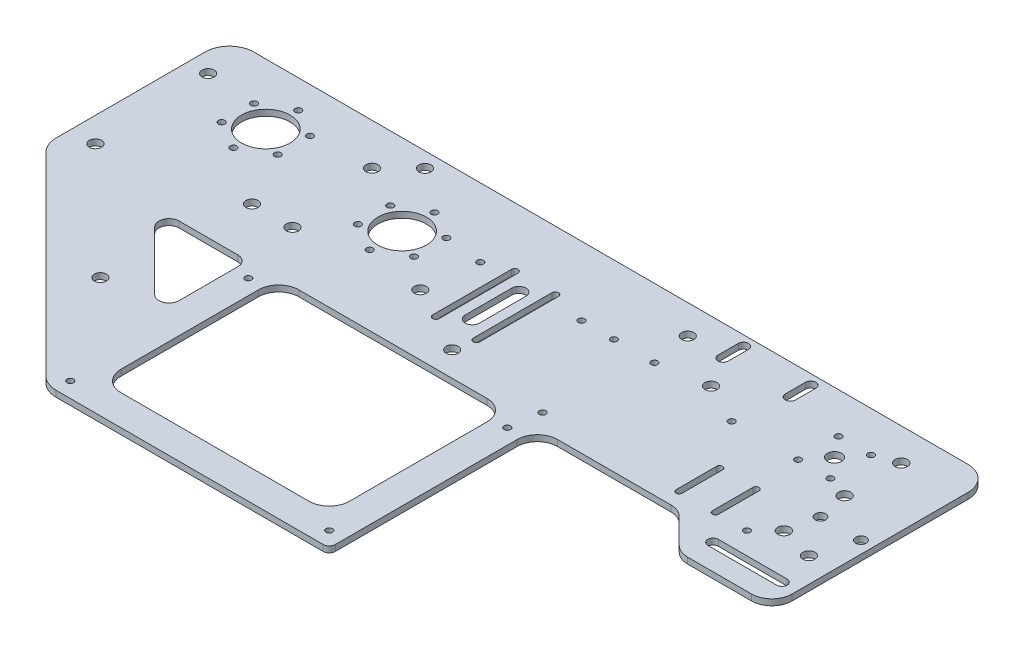
SolidWorks part; units mm, degrees
material "ACM"
ref_plane "Plano frontal" through (0, 0, 0) normal (0, 0, 1) x (1, 0, 0)
ref_plane "Plano superior" through (0, 0, 0) normal (0, 1, 0) x (1, 0, 0)
ref_plane "Plano direito" through (0, 0, 0) normal (1, 0, 0) x (0, 0, -1)
sketch "Esboço1" plane through (0, 0, 0) normal (0, 1, 0) x (1, 0, 0)
  line L3 (-80.5574, -153.6487) -> (51.4721, -153.6487)
  line L4 (54.4721, -150.6487) -> (54.4721, -60.7886)
  line L6 (188.5279, -40.7886) -> (188.5279, 28)
  line L7 (176.5279, 40) -> (-176.5279, 40)
  line L8 (-188.5279, 28) -> (-188.5279, -45.6781)
  line L12 (-122.5768, -50.7886) -> (-93.5279, -50.7886)
  line L13 (-88.5279, -55.7886) -> (-88.5279, -84.8375)
  line L14 (-97.0635, -88.373) -> (-126.1124, -59.3241)
  line L15 (39.4721, -60.6487) -> (39.4721, -128.6487)
  line L16 (29.4721, -138.6487) -> (-63.5279, -138.6487)
  line L17 (-73.5279, -128.6487) -> (-73.5279, -60.6487)
  line L18 (-63.5279, -50.6487) -> (29.4721, -50.6487)
  line L20 (132.5279, 0) -> (148.5279, 0) construction
  line L21 (132.5279, 0) -> (132.5279, 20) construction
  line L22 (132.5279, 20) -> (148.5279, 20) construction
  line L23 (148.5279, 0) -> (148.5279, 20) construction
  line L24 (132.5279, 0) -> (148.5279, 20) construction
  line L25 (132.5279, 20) -> (148.5279, 0) construction
  line L30 (64.4721, -50.7886) -> (178.5279, -50.7886)
  line L31 (134.7221, -43) -> (134.7221, -23) construction
  line L32 (133.2221, -43) -> (133.2221, -23)
  line L33 (136.2221, -43) -> (136.2221, -23)
  line L34 (125.7221, -45.2211) -> (125.7221, -21.4375) construction
  line L36 (116.7221, -43) -> (116.7221, -23) construction
  line L37 (118.2221, -43) -> (118.2221, -23)
  line L38 (115.2221, -43) -> (115.2221, -23)
  line L40 (54.4721, -120.5) -> (144.9721, -120.5) construction
  line L41 (54.4721, -120.5) -> (54.4721, -7) construction
  line L42 (54.4721, -7) -> (144.9721, -7) construction
  line L43 (144.9721, -120.5) -> (144.9721, -7) construction
  line L44 (54.4721, -120.5) -> (144.9721, -7) construction
  line L45 (54.4721, -7) -> (144.9721, -120.5) construction
  line L46 (70.5279, 25) -> (70.5279, 35) construction
  line L47 (67.9779, 25) -> (67.9779, 35)
  line L48 (73.0779, 25) -> (73.0779, 35)
  line L49 (103.7779, 25) -> (103.7779, 35) construction
  line L50 (101.2279, 25) -> (101.2279, 35)
  line L51 (106.3279, 25) -> (106.3279, 35)
  line L52 (-185.0132, -54.1634) -> (-89.0426, -150.134)
  circle A0 centre (-81.0279, -58.1487) radius 1.6
  circle A1 centre (-81.0279, -146.1487) radius 1.6
  circle A2 centre (46.9721, -58.1487) radius 1.6
  circle A3 centre (46.9721, -146.1487) radius 1.6
  circle A8 centre (176.311, -38.4318) radius 3
  circle A9 centre (0, -38.4318) radius 3
  circle A11 centre (-140.5279, 10) radius 12
  circle A20 centre (-140.5279, 10) radius 16 construction
  circle A21 centre (-140.5279, -6) radius 1.6
  circle A22 centre (-154.3843, 2) radius 1.6
  circle A23 centre (-154.3843, 18) radius 1.6
  circle A24 centre (-84.3674, 32.5) radius 3
  circle A25 centre (-176.311, -38.4318) radius 3
  circle A26 centre (140.5279, 10) radius 3.5
  circle A27 centre (148.5279, 0) radius 1.6
  circle A28 centre (148.5279, 20) radius 1.6
  circle A29 centre (132.5279, 0) radius 1.6
  circle A30 centre (132.5279, 20) radius 1.6
  arc A31 (51.4721, -153.6487) -> (54.4721, -150.6487) centre (51.4721, -150.6487) ccw
  arc A34 (188.5279, 28) -> (176.5279, 40) centre (176.5279, 28) ccw
  arc A35 (-176.5279, 40) -> (-188.5279, 28) centre (-176.5279, 28) ccw
  arc A39 (-93.5279, -50.7886) -> (-88.5279, -55.7886) centre (-93.5279, -55.7886) cw
  arc A40 (-88.5279, -84.8375) -> (-97.0635, -88.373) centre (-93.5279, -84.8375) cw
  arc A41 (-126.1124, -59.3241) -> (-122.5768, -50.7886) centre (-122.5768, -55.7886) cw
  arc A42 (39.4721, -128.6487) -> (29.4721, -138.6487) centre (29.4721, -128.6487) cw
  arc A43 (-63.5279, -138.6487) -> (-73.5279, -128.6487) centre (-63.5279, -128.6487) cw
  arc A44 (-73.5279, -60.6487) -> (-63.5279, -50.6487) centre (-63.5279, -60.6487) cw
  arc A45 (29.4721, -50.6487) -> (39.4721, -60.6487) centre (29.4721, -60.6487) cw
  circle A46 centre (-140.5279, 26) radius 1.6
  circle A47 centre (-126.6715, 18) radius 1.6
  circle A48 centre (-126.6715, 2) radius 1.6
  circle A49 centre (-63.1716, 0) radius 16 construction
  circle A50 centre (-63.1716, -16) radius 1.6
  circle A51 centre (-77.028, -8) radius 1.6
  circle A52 centre (-77.028, 8) radius 1.6
  circle A53 centre (-63.1716, 16) radius 1.6
  circle A54 centre (-49.3152, 8) radius 1.6
  circle A55 centre (-49.3152, -8) radius 1.6
  circle A56 centre (-63.1716, 0) radius 12
  circle A57 centre (-33.5279, -20.6487) radius 3
  circle A58 centre (79.5279, 10) radius 3
  arc A62 (188.5279, -40.7886) -> (178.5279, -50.7886) centre (178.5279, -40.7886) cw
  arc A63 (54.4721, -60.7886) -> (64.4721, -50.7886) centre (64.4721, -60.7886) cw
  arc A64 (133.2221, -43) -> (136.2221, -43) centre (134.7221, -43) ccw
  arc A65 (136.2221, -23) -> (133.2221, -23) centre (134.7221, -23) ccw
  arc A66 (118.2221, -43) -> (115.2221, -43) centre (116.7221, -43) cw
  arc A67 (115.2221, -23) -> (118.2221, -23) centre (116.7221, -23) cw
  circle A68 centre (99.7221, 0) radius 1.6
  circle A69 centre (49.2221, -43) radius 1.6
  circle A70 centre (134.7221, -43) radius 1.6 construction
  circle A71 centre (-30.5279, 6) radius 1.6
  circle A72 centre (19.4721, 6) radius 1.6
  circle A73 centre (55.5279, 6) radius 1.6
  circle A75 centre (35.5279, 6) radius 1.6
  circle A76 centre (70.5279, 30) radius 2.55 construction
  circle A77 centre (103.7779, 30) radius 2.55 construction
  circle A78 centre (159.4679, 24.07) radius 3.05
  circle A79 centre (159.4679, -3.93) radius 3.05
  circle A80 centre (159.4679, -33.93) radius 3.05
  arc A81 (67.9779, 25) -> (73.0779, 25) centre (70.5279, 25) ccw
  arc A82 (73.0779, 35) -> (67.9779, 35) centre (70.5279, 35) ccw
  arc A83 (101.2279, 25) -> (106.3279, 25) centre (103.7779, 25) ccw
  arc A84 (106.3279, 35) -> (101.2279, 35) centre (103.7779, 35) ccw
  circle A85 centre (-178.5279, 19.5) radius 3
  circle A86 centre (-97.5279, 19.5) radius 3
  arc A87 (-80.5574, -153.6487) -> (-89.0426, -150.134) centre (-80.5574, -141.6487) cw
  arc A88 (-185.0132, -54.1634) -> (-188.5279, -45.6781) centre (-176.5279, -45.6781) cw
  circle A89 centre (52.3279, 25.68) radius 3
  circle A90 centre (150.2221, -43) radius 1.6
  point P14 (134.7221, -33)
  point P43 (-140.5279, 10)
  point P70 (-144.4721, -50.6487)
  point P82 (-85.5279, -153.6487)
  point P116 (-63.1716, 0)
  point P123 (0, 40)
  point P124 (116.7221, -33)
  point P129 (99.7221, -63.75)
  point P141 (99.7221, -7)
  point P161 (70.5279, 30)
  point P168 (103.7779, 30)
  dimension "D2" = 3
  dimension "D8" = 12
  dimension "D10" = 12
  dimension "D11" = 61
  dimension "D12" = 203.9448
  dimension "D13" = 7.5
  dimension "D14" = 104.1605
  dimension "D16" = 135.7229
  dimension "D20" = 19.68
  dimension "D21" = 3.2
  dimension "D22" = 48.4318
  dimension "D23" = 32
  dimension "D24" = 3.2
  dimension "D25" = 6
  dimension "D26" = 24
  dimension "D27" = 48
  dimension "D28" = 30
  dimension "D29" = 40
  dimension "D30" = 6
  dimension "D34" = 30
  dimension "D31" = 32
  dimension "D32" = 3.2
  dimension "D33" = 24
  dimension "D35" = 6
  dimension "D36" = 155
  dimension "D37" = 30
  dimension "D44" = 7
  dimension "D48" = 10
  dimension "D54" = 50.5
  dimension "D6" = 10
  dimension "D58" = 5
  dimension "D62" = 1.5
  dimension "D72" = 85
  dimension "D75" = 5.1
  dimension "D80" = 14.07
  dimension "D82" = 6.1
  dimension "D83" = 10
  dimension "D19" = 6
  dimension "D47" = 101
  dimension "D1" = 137
  dimension "D9" = 377.0558
  dimension "D15" = 225
  dimension "D17" = 38
  dimension "D18" = 15
  dimension "D38" = 48
  dimension "D39" = 15
  dimension "D40" = 12.2169
  dimension "D41" = 12.2169
  dimension "D42" = 16
  dimension "D43" = 20
  dimension "D45" = 15
  dimension "D46" = 15
  dimension "D49" = 7.5
  dimension "D50" = 7.5
  dimension "D51" = 88
  dimension "D52" = 128
  dimension "D53" = 93
  dimension "D56" = 20.6487
  dimension "D57" = 68
  dimension "D59" = 10
  dimension "D60" = 20.5
  dimension "D61" = 20
  dimension "D63" = 9
  dimension "D64" = 113.5
  dimension "D65" = 90.5
  dimension "D66" = 7
  dimension "D67" = 43
  dimension "D69" = 34
  dimension "D70" = 110
  dimension "D71" = 50
  dimension "D73" = 20
  dimension "D74" = 33.25
  dimension "D76" = 10
  dimension "D77" = 15
  dimension "D78" = 30
  dimension "D79" = 28
  dimension "D81" = 18.94
  dimension "D84" = 81
extrude "Ressalto-extrusão1" add sketch "Esboço1" against normal blind 3
sketch "Esboço2" plane through (0, 0, 0) normal (0, 1, 0) x (1, 0, 0)
  line L0 (188.5279, -40.7886) -> (188.5279, 28) construction
  line L1 (-126.1124, -59.3241) -> (-97.0635, -88.373) construction
  line L2 (-131.2731, -107.9035) -> (-104.403, -81.0335) construction
  line L3 (-185.0132, -54.1634) -> (-89.0426, -150.134) construction
  line L4 (159.4679, -6.98) -> (159.4679, -30.88) construction
  line L5 (-140.5279, 10) -> (-63.1716, 0) construction
  line L6 (176.5279, 40) -> (-176.5279, 40) construction
  line L7 (-91.8498, -25.5) -> (-111.8498, -25.5) construction
  circle A1 centre (-117.8381, -94.4685) radius 3
  arc A2 (-188.5279, -45.6781) -> (-185.0132, -54.1634) centre (-176.5279, -45.6781) ccw construction
  circle A3 centre (182.5279, -18.93) radius 2.6
  circle A4 centre (162.5279, -18.93) radius 2.6
  circle A7 centre (-111.8498, -25.5) radius 3
  circle A8 centre (-91.8498, -25.5) radius 3
  circle A9 centre (159.4679, -3.93) radius 3.05 construction
  circle A10 centre (159.4679, -33.93) radius 3.05 construction
  point P1 (-117.8381, -94.4685)
  point P18 (159.4679, -18.93)
  point P30 (-101.8498, 5)
  point P41 (-101.8498, -25.5)
  dimension "D1" = 76
  dimension "D2" = 6
  dimension "D3" = 20
  dimension "D4" = 5.2
  dimension "D5" = 6
  dimension "D6" = 6
  dimension "D7" = 65.5
  dimension "D8" = 20
extrude "Corte-extrusão1" cut sketch "Esboço2" against normal blind 10
sketch "Esboço3" plane through (0, 0, 0) normal (0, 1, 0) x (1, 0, 0)
  line L0 (142.7858, -68.9886) -> (114.5858, -40.7886)
  line L1 (188.5279, -40.7886) -> (142.7858, -40.7886)
  line L2 (188.5279, -40.7886) -> (188.5279, -68.9886)
  line L3 (188.5279, -68.9886) -> (142.7858, -68.9886)
  line L4 (142.7858, -40.7886) -> (142.7858, -68.9886)
  line L5 (114.5858, -40.7886) -> (142.7858, -40.7886)
  line L6 (180.9279, -56.3886) -> (146.9279, -56.3886) construction
  line L7 (180.9279, -58.9886) -> (146.9279, -58.9886)
  line L8 (180.9279, -53.7886) -> (146.9279, -53.7886)
  line L10 (133.2221, -23) -> (133.2221, -43) construction
  line L11 (136.2221, -43) -> (136.2221, -23) construction
  line L12 (133.2221, -23) -> (133.2221, -43)
  line L13 (136.2221, -43) -> (136.2221, -23)
  line L14 (115.2221, -23) -> (115.2221, -43) construction
  line L15 (118.2221, -43) -> (118.2221, -23) construction
  line L16 (115.2221, -23) -> (115.2221, -43)
  line L17 (118.2221, -43) -> (118.2221, -23)
  line L18 (64.4721, -50.7886) -> (178.5279, -50.7886) construction
  arc A0 (180.9279, -58.9886) -> (180.9279, -53.7886) centre (180.9279, -56.3886) ccw
  arc A1 (146.9279, -53.7886) -> (146.9279, -58.9886) centre (146.9279, -56.3886) ccw
  circle A2 centre (176.311, -38.4318) radius 3 construction
  arc A3 (133.2221, -43) -> (136.2221, -43) centre (134.7221, -43) ccw construction
  circle A4 centre (176.311, -38.4318) radius 3
  arc A5 (133.2221, -43) -> (136.2221, -43) centre (134.7221, -43) ccw
  arc A6 (115.2221, -43) -> (118.2221, -43) centre (116.7221, -43) ccw construction
  arc A7 (115.2221, -43) -> (118.2221, -43) centre (116.7221, -43) ccw
  circle A8 centre (150.2221, -43) radius 1.6 construction
  circle A9 centre (150.2221, -43) radius 1.6
  point P8 (163.9279, -56.3886)
  point P13 (183.5279, -56.3886)
  point P16 (144.3279, -56.3886)
  dimension "D3" = 2.6
  dimension "D1" = 45
  dimension "D2" = 34
  dimension "D4" = 10
  dimension "D5" = 10
  dimension "D6" = 5
  dimension "D7" = 3
extrude "Ressalto-extrusão2" add sketch "Esboço3" against normal up to surface (3 mm away) contours L5 L0 L4 | L1 L4 L3 L2 A1 L8 A0 L7 region at (143.3231, 0, 54.8886) region at (133.6258, 0, 50.5324) up to face at (-117.8381, -3, 91.4685)
fillet "Filete1" radius 10 3 edges at (188.5279, -1.5, 68.9886) (142.7858, -1.5, 68.9886) (124.5858, -1.5, 50.7886)
sketch "Esboço4" plane through (0, 0, 0) normal (0, 1, 0) x (1, 0, 0)
  line L0 (-63.1716, 0) -> (140.5279, 10) construction
  line L1 (-8.1716, 2.7001) -> (-8.1716, -20.2999) construction
  line L2 (-4.6716, 2.7001) -> (-4.6716, -20.2999)
  line L3 (-11.6716, 2.7001) -> (-11.6716, -20.2999)
  line L4 (1.8284, 10.7001) -> (1.8284, -12.2999) construction
  line L5 (3.4284, 10.7001) -> (3.4284, -12.2999)
  line L6 (0.2284, 10.7001) -> (0.2284, -12.2999)
  line L7 (1.8284, -5.2999) -> (1.8284, -28.2999) construction
  line L8 (3.4284, -5.2999) -> (3.4284, -28.2999)
  line L9 (0.2284, -5.2999) -> (0.2284, -28.2999)
  line L10 (-8.1716, 2.7001) -> (-8.1716, 10.7001) construction
  line L11 (-18.1716, -5.2999) -> (-18.1716, -28.2999) construction
  line L12 (-19.7716, -5.2999) -> (-19.7716, -28.2999)
  line L13 (-16.5716, -5.2999) -> (-16.5716, -28.2999)
  line L14 (-18.1716, 10.7001) -> (-18.1716, -12.2999) construction
  line L15 (-19.7716, 10.7001) -> (-19.7716, -12.2999)
  line L16 (-16.5716, 10.7001) -> (-16.5716, -12.2999)
  arc A0 (-4.6716, 2.7001) -> (-11.6716, 2.7001) centre (-8.1716, 2.7001) ccw
  arc A1 (-11.6716, -20.2999) -> (-4.6716, -20.2999) centre (-8.1716, -20.2999) ccw
  arc A2 (3.4284, 10.7001) -> (0.2284, 10.7001) centre (1.8284, 10.7001) ccw
  arc A3 (0.2284, -12.2999) -> (3.4284, -12.2999) centre (1.8284, -12.2999) ccw
  arc A4 (3.4284, -5.2999) -> (0.2284, -5.2999) centre (1.8284, -5.2999) ccw
  arc A5 (0.2284, -28.2999) -> (3.4284, -28.2999) centre (1.8284, -28.2999) ccw
  circle A6 centre (-63.1716, 16) radius 1.6 construction
  arc A7 (-19.7716, -5.2999) -> (-16.5716, -5.2999) centre (-18.1716, -5.2999) cw
  arc A8 (-16.5716, -28.2999) -> (-19.7716, -28.2999) centre (-18.1716, -28.2999) cw
  arc A9 (-19.7716, 10.7001) -> (-16.5716, 10.7001) centre (-18.1716, 10.7001) cw
  arc A10 (-16.5716, -12.2999) -> (-19.7716, -12.2999) centre (-18.1716, -12.2999) cw
  circle A11 centre (140.5279, 10) radius 3.5 construction
  point P6 (-8.1716, -8.7999)
  point P11 (1.8284, -0.7999)
  point P18 (1.8284, -16.7999)
  point P31 (-18.1716, -16.7999)
  point P38 (-18.1716, -0.7999)
  dimension "D1" = 16
  dimension "D2" = 23
  dimension "D3" = 20
  dimension "D4" = 8
  dimension "D5" = 55
extrude "Corte-extrusão2" cut sketch "Esboço4" against normal through all contours L6 A3 L5 A2 | L9 A5 L8 A4 | L3 A1 L2 A0 | L12 A8 L13 A7 | L15 A10 L16 A9
